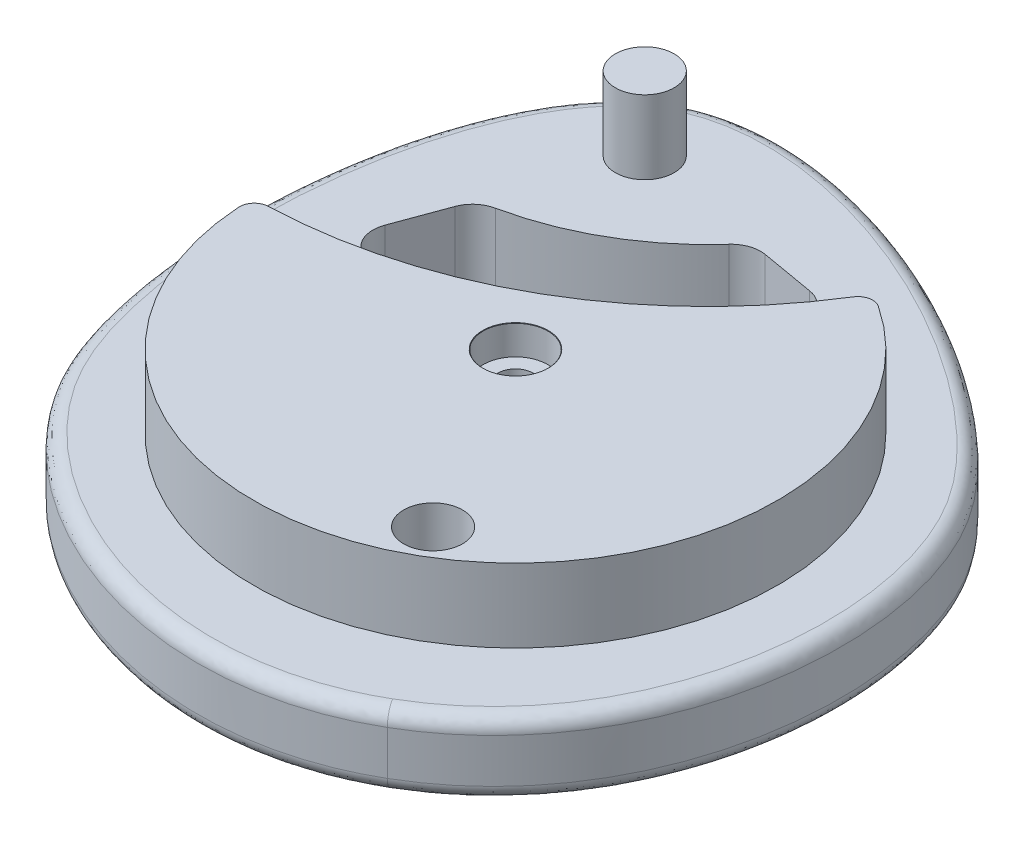
SolidWorks part; units mm, degrees
note: The reader was unsure of these and kept them because the rebuilt part matched: shared geometry of "Sketch1<3>", "Sketch2<4>".
ref_plane "Front Plane" through (0, 0, 0) normal (0, 0, 1) x (1, 0, 0)
ref_plane "Top Plane" through (0, 0, 0) normal (0, 1, 0) x (1, 0, 0)
ref_plane "Right Plane" through (0, 0, 0) normal (1, 0, 0) x (0, 0, -1)
sketch "Sketch1" plane through (0, 0, 0) normal (0, 1, 0) x (1, 0, 0)
  line L0 (0, 0) -> (48, 0)
  line L1 (48, 0) -> (36, 20.7846)
  line L2 (36, 20.7846) -> (0, 0)
  line L3 (48, 0) -> (30.2, 30.8305)
  line L4 (30.2, 30.8305) -> (30.2, 0)
  line L5 (36, 20.7846) -> (32.5, 26.8468) construction
  circle A0 centre (48, 0) radius 17.8
  arc A1 (30.2, 0) -> (56.9, 15.4153) centre (30.2, 30.8305) ccw
  circle A2 centre (36, 20.7846) radius 2
  circle A3 centre (48, 0) radius 31
  point P10 (30.2, 0)
  dimension "D4" = 17.8
  dimension "D6" = 4
  dimension "D1" = 48
  dimension "D2" = 41.5692
  dimension "D3" = 24
  dimension "D5" = 30.8305
  dimension "D7" = 7
extrude "Boss-Extrude1" add sketch "Sketch1" against normal blind 5 contours L0 A3 L3 A2 A0 | A1 L0 L1 | A0 A1 L3 | L3 A1 A0 | A1 L1 L0 A0 | A2 L2 L4 A0 L3 | L2 A3 L0 L4 | L4 A3 L2 | L3 A3 L4 L2 A2 | L1 A2 L3 | L3 A2 L2 | L2 A2 L1
extrude "Boss-Extrude2" add sketch "Sketch1<3>" along normal blind 5 contours L1 A2 L3 | L3 A2 L2 | L2 A2 L1 | A1 L1 L0 A0 | A1 L0 L1
sketch "Sketch1<3>" plane through (0, 0, 0) normal (0, 1, 0) x (1, 0, 0) same geometry as "Sketch1"
sketch "Sketch2" plane through (0, -5, 0) normal (0, -1, 0) x (1, 0, 0)
  line L0 (36, -20.7846) -> (63.5, 26.8468) construction
  line L1 (36, -20.7846) -> (33.5, -25.1147) construction
  line L2 (26.1894, -20.894) -> (39.599, -28.636) construction
  line L3 (30.2, -5) -> (32.9309, -12.4321)
  line L4 (52.5699, -17.9153) -> (44.7681, -19.2663)
  circle A0 centre (36, -20.7846) radius 2 construction
  arc A1 (56.9, -15.4153) -> (30.2, 0) centre (30.2, -30.8305) ccw construction
  arc A2 (56.9, -15.4153) -> (30.2, 0) centre (48, 0) ccw construction
  circle A3 centre (36, -20.7846) radius 2
  arc A4 (56.9, -15.4153) -> (30.2, 0) centre (30.2, -30.8305) ccw
  arc A5 (56.9, -15.4153) -> (30.2, 0) centre (48, 0) ccw
  circle A6 centre (48, 0) radius 31 construction
  circle A7 centre (48, 0) radius 31
  circle A8 centre (55.65, 13.2502) radius 2
  arc A9 (52.5699, -17.9153) -> (30.2, -5) centre (30.2, -30.8305) ccw
  arc A10 (44.7681, -19.2663) -> (32.9309, -12.4321) centre (30.2, -30.8305) ccw
  spline S0 degree 3 poles (33.5, -25.1147) (25.9949, -20.7817) (23.409, -1.3035) (31.6125, 19.6967) (48.7553, 27.0458) (59.9, 20.6114) knots 0 0 0 0 0.48256 0.567978 1 1 1 1
  spline S1 degree 3 poles (33.5, -25.1147) (41.0051, -29.4478) (59.1666, -21.9482) (73.2516, -4.3437) (71.0447, 14.177) (59.9, 20.6114) knots 0 0 0 0 0.48256 0.567978 1 1 1 1
  point P2 (37, -19.0526)
  point P18 (56.9, 15.4153)
  point P19 (43.1153, -8.4606)
  point P22 (35, -22.5167)
  point P23 (60, 28.1796)
  point P25 (56.9, 15.4153)
  point P26 (45.6153, -4.1305)
  point P28 (39.5, -14.7224)
  point P29 (34.977, 12.7985)
  point P30 (27.0178, 10.9315)
  point P33 (42.1551, 23.5953)
  point P34 (25.9295, 9.3947)
  point P35 (43.1153, 23.2985)
  point P36 (45.6153, 23.5953)
  point P37 (28.2051, 11.0919)
  point P39 (45.6153, 24.9804)
  point P40 (48, 23.2196)
  point P41 (55.9, 13.6832)
  point P42 (52.5699, 8.7196)
  point P43 (0, 0)
  circle M8 centre (48, 0) radius 31
  dimension "D2" = 3
  dimension "D4" = 4
  dimension "D5" = 5
  dimension "D1" = 6
  dimension "D3" = 0
  dimension "D6" = 5
  dimension "D7" = 2.5
extrude "Cut-Extrude3" cut sketch "Sketch2" against normal through all contours S1 S0 M8 | A8
extrude "Cut-Extrude4" cut sketch "Sketch2<4>" against normal through all contours A10 L4 A9 L3
sketch "Sketch2<4>" plane through (0, -5, 0) normal (0, -1, 0) x (1, 0, 0) same geometry as "Sketch2"
fillet "Fillet1" radius 2 4 edges at (32.9309, -2.5, -12.4321) (44.7681, -2.5, -19.2663) (30.2, -2.5, -5) (52.5699, -2.5, -17.9153)
sketch "Sketch3" plane through (0, -5, 0) normal (0, -1, 0) x (1, 0, 0)
  line L1 (62.2172, 13.6832) -> (60.0586, 17.422)
  line L2 (60.0586, 17.422) -> (55.7414, 17.422)
  line L3 (55.7414, 17.422) -> (53.5828, 13.6832)
  line L4 (53.5828, 13.6832) -> (55.7414, 9.9444)
  line L5 (55.7414, 9.9444) -> (60.0586, 9.9444)
  line L6 (60.0586, 9.9444) -> (62.2172, 13.6832)
sketch "Sketch4" plane through (0, -5, 0) normal (0, -1, 0) x (1, 0, 0)
  arc A0 (56.9, -15.4153) -> (30.2, 0) centre (48, 0) ccw construction
  arc A1 (56.9, -15.4153) -> (30.2, 0) centre (48, 0) ccw
  circle A2 centre (48, 0) radius 4.5
  spline S2 degree 3 poles (2335.6073, 1890.9669) (-289.9376, -48.3971) (25.6238, -63.8728) (104.42, 34.6132) (-121.4879, 344.7161) (-1204.1296, -2686.2197) knots -2.381466 -2.381466 -2.381466 -2.381466 0.48256 0.567978 3.212887 3.212887 3.212887 3.212887 only from (33.5, -25.1147) to (59.9, 20.6114)
  spline S3 degree 3 poles (33.5, -25.1147) (41.0051, -29.4478) (59.1666, -21.9482) (73.2516, -4.3437) (71.0447, 14.177) (59.9, 20.6114) knots 0 0 0 0 0.48256 0.567978 1 1 1 1
  spline S4 degree 3 poles (-1652.2908, -2427.5107) (431.2793, 25.5769) (49.766, 66.1679) (3.8727, -51.3145) (175.0542, -316.8588) (541.8168, 2926.5662) knots -2.212895 -2.212895 -2.212895 -2.212895 0.432022 0.51744 3.381454 3.381454 3.381454 3.381454 only from (59.9, 20.6114) to (33.5, -25.1147)
  spline S5 degree 3 poles (59.9, 20.6114) (48.7553, 27.0458) (31.6125, 19.6967) (23.409, -1.3035) (25.9949, -20.7817) (33.5, -25.1147) knots 0 0 0 0 0.432022 0.51744 1 1 1 1
  dimension "D2" = 9
  dimension "D1" = 0
extrude "Cut-Extrude7" cut sketch "Sketch4" against normal blind 4 contours A2
fillet "Fillet2" radius 1 2 edges at (30.2, 2.5, 0) (56.9, 2.5, -15.4153)
fillet "Fillet5" radius 1 2 edges
fillet "Fillet6" radius 1 2 edges
hole_wizard "CBORE for M2 SHCS1" positions "Sketch5" profile "Sketch7" counterbore size "M2" standard "ANSI Metric"
sketch "Sketch5" plane through (0, 5, 0) normal (0, 1, 0) x (1, 0, 0)
  point P0 (48, 0)
sketch "Sketch7" plane through (48, 5, 0) normal (1, 0, 0) x (0, 0, 1)
  line L0 (0, 0) -> (0, 15.721)
  line L1 (0, 15.721) -> (1.2, 15)
  line L2 (1.2, 15) -> (1.2, 2)
  line L3 (1.2, 2) -> (2.2, 2)
  line L5 (2.2, 2) -> (2.2, 0.025)
  line L6 (2.2, 0.025) -> (2.225, 0)
  line L7 (2.225, 0) -> (0, 0)
  line L8 (-2.2, 0.025) -> (-2.225, 0) construction
  line L10 (0, 15.721) -> (-1.2, 15) construction
  line L11 (0, -6.35) -> (0, 107.95) construction
  dimension "Hole Dia." = 2.4
  dimension "Hole Depth" = 15
  dimension "C'Bore Dia." = 4.4
  dimension "C'Bore Depth" = 2
  dimension "Near C'Sink Dia." = 4.45
  dimension "Near C'Sink Angle" = 90
  dimension "Drill Angle" = 118
sketch "Sketch8" plane through (0, -5, 0) normal (0, -1, 0) x (1, 0, 0)
  line L0 (48, 0) -> (55.65, 13.2502) construction
  line L2 (48.384, 2.6651) -> (50.384, 6.1292)
  line L3 (48.384, 2.6651) -> (50.116, 1.6651)
  line L4 (50.116, 1.6651) -> (52.116, 5.1292)
  line L5 (50.384, 6.1292) -> (52.116, 5.1292)
  line L6 (48.384, 2.6651) -> (52.116, 5.1292) construction
  line L7 (50.116, 1.6651) -> (50.384, 6.1292) construction
  circle A0 centre (48, 0) radius 4.5 construction
  point P4 (50.25, 3.8971)
  dimension "D1" = 2
  dimension "D2" = 2
extrude "Cut-Extrude8" cut sketch "Sketch8" against normal up to surface (4 mm away) up to face at (48, -1, -1.2)
equation "\"DrivenWheelD\"= 80"
equation "\"DriverD\"= 35"
equation "\"PinD\"= 4"
equation "\"a\" = 24"
equation "\"b\" = sqr ( \"c\" ^ 2 - \"a\" ^ 2 )"
equation "\"c\" = \"a\" / sin ( 180 / \"n\" )"
equation "\"s\" = \"a\" + \"b\" - \"c\""
equation "\"w\"= ( \"p\" + \"t\" )"
equation "\"y\"= \"a\" - ( \"p\" * 1.5 )"
equation "\"z\" = \"y\" - \"t\""
equation "\"p\"= 4"
equation "\"n\" = 6"
equation "\"t\"= 0.2"
equation "\"v\" = \"b\" * \"z\" / \"a\""
equation "\"D1@Sketch1\"=\"c\""
equation "\"D2@Sketch1\"=\"b\""
equation "\"D3@Sketch1\"=\"a\""
equation "\"D4@Sketch1\"=\"z\""
equation "\"D5@Sketch1\"=\"v\""
equation "\"D6@Sketch1\"=\"p\""
equation "\"D7@Sketch1\"=\"p\"+3"
